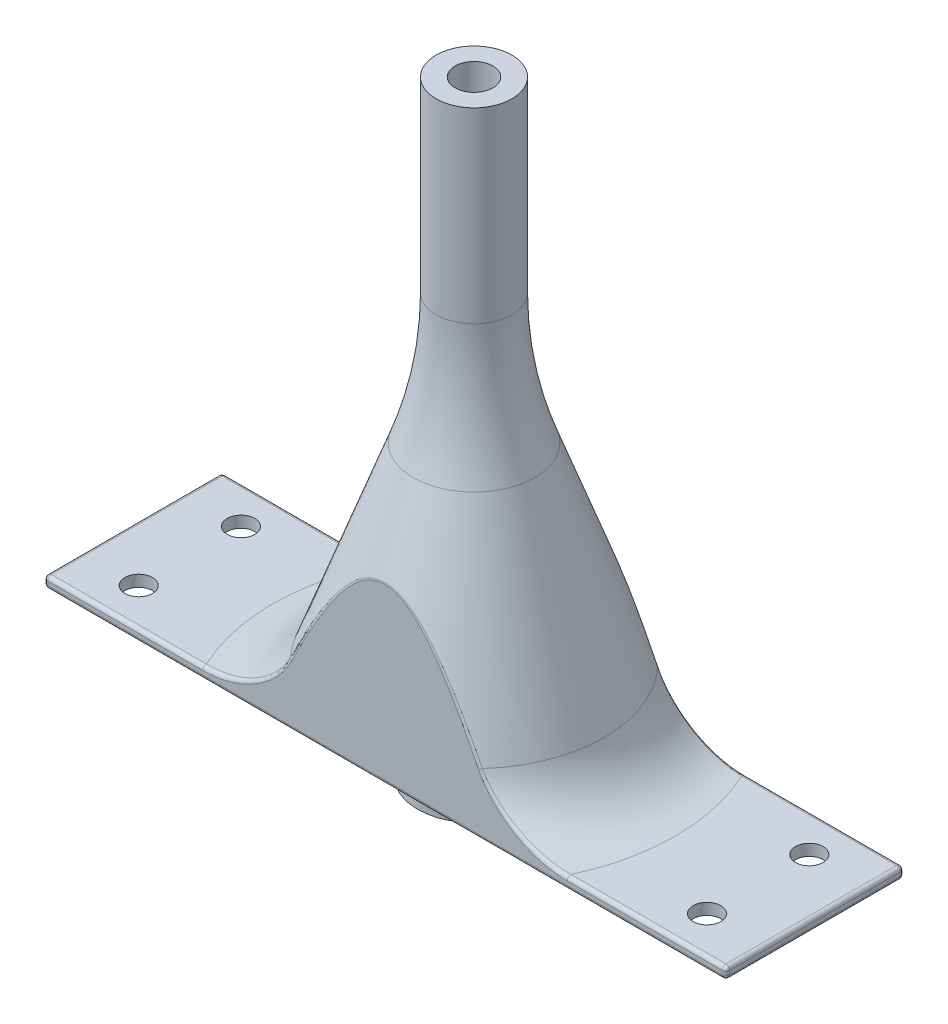
SolidWorks part; units mm, degrees
ref_plane "Alzado" through (0, 0, 0) normal (0, 0, 1) x (1, 0, 0)
ref_plane "Planta" through (0, 0, 0) normal (0, 1, 0) x (1, 0, 0)
ref_plane "Vista lateral" through (0, 0, 0) normal (1, 0, 0) x (0, 0, -1)
sketch "Croquis1" plane through (0, 0, 0) normal (0, 1, 0) x (1, 0, 0)
  circle A0 centre (0, 0) radius 10
  dimension "D1" = 20
extrude "Saliente-Extruir1" add sketch "Croquis1" along normal blind 150 and the other way blind 10
sketch "Croquis5" plane through (0, 150, 0) normal (0, -1, 0) x (1, 0, 0)
  circle A0 centre (0, 0) radius 5
  dimension "D1" = 10
extrude "Cortar-Extruir1" cut sketch "Croquis5" against normal through all both and the other way through all
sketch "Croquis6" plane through (0, 0, 0) normal (0, 1, 0) x (1, 0, 0)
  line L0 (-90, 13.5) -> (-75, 13.5) construction
  line L1 (-90, 23.5) -> (90, 23.5)
  line L2 (-90, 23.5) -> (-90, -23.5)
  line L3 (-90, -23.5) -> (90, -23.5)
  line L4 (90, 23.5) -> (90, -23.5)
  line L5 (-90, 23.5) -> (90, -23.5) construction
  line L6 (-90, -23.5) -> (90, 23.5) construction
  line L7 (-75, 13.5) -> (-75, 23.5) construction
  line L8 (-18.619, 0) -> (0, 0) construction
  line L9 (0, 0) -> (0, 19.4113) construction
  circle A0 centre (-75, 13.5) radius 3.65
  circle A1 centre (75, 13.5) radius 3.65
  circle A2 centre (75, -13.5) radius 3.65
  circle A3 centre (-75, -13.5) radius 3.65
  circle A4 centre (0, 0) radius 5
  point P0 (0, 0)
  dimension "D5" = 7.3
  dimension "D1" = 47
  dimension "D2" = 180
  dimension "D3" = 15
  dimension "D4" = 10
  dimension "D6" = 75
  dimension "D7" = 13.5
extrude "Saliente-Extruir2" add sketch "Croquis6" along normal blind 3
chamfer "Chaflán1" distance 80 angle 20 1 edges at (0, 3, 10) first distance on face at (0, 3, 10)
fillet "Redondeo1" radius 20 2 edges at (-39.1176, 3, 0) (39.1176, 3, 0)
fillet "Redondeo2" radius 1 20 edges at (35.6523, 5.9296, -23.5) (-1.7026, 45.7398, -23.5) (90, 1.5, -23.5) (68.8205, 3, -23.5) (90, 0, 0) (0, 0, -23.5) (-37.6411, 5.0143, -23.5) (90, 3, 0) (90, 1.5, 23.5) (0, 0, 23.5) (-90, 0, 0) (-90, 1.5, -23.5) (-68.8205, 3, -23.5) (68.8205, 3, 23.5) (-90, 1.5, 23.5) (-90, 3, 0) (37.6411, 5.0143, 23.5) (-68.8205, 3, 23.5) (1.7026, 45.7398, 23.5) (-35.6523, 5.9296, 23.5)
sketch "Croquis7" plane through (0, -10, 0) normal (0, -1, 0) x (1, 0, 0)
  circle A0 centre (0, 0) radius 5
  circle A1 centre (0, 0) radius 14.85
  dimension "D1" = 29.7
  dimension "D2" = 10
extrude "Saliente-Extruir3" add sketch "Croquis7" against normal blind 10
fillet "Redondeo4" radius 3 1 edges at (0, 0, -14.85)
fillet "Redondeo5" radius 100 1 edges at (0, 83, 10)
